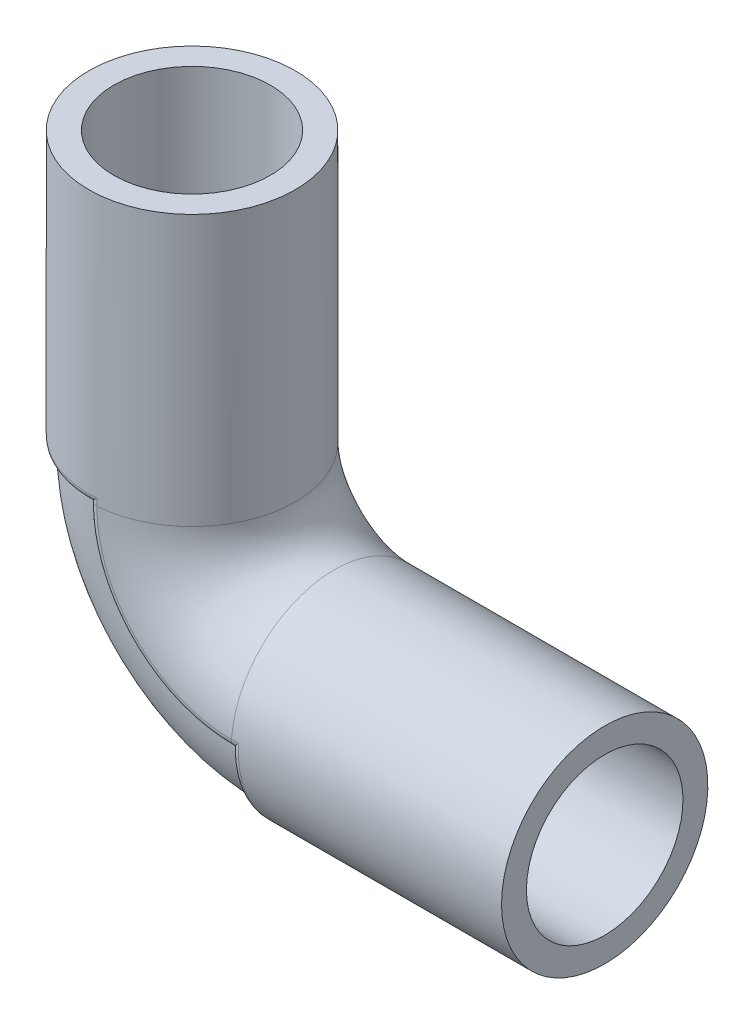
SolidWorks part; units mm, degrees
material "PVC 0.007 Plasticized"
ref_plane "Front Plane" through (0, 0, 0) normal (0, 0, 1) x (1, 0, 0)
ref_plane "Top Plane" through (0, 0, 0) normal (0, 1, 0) x (1, 0, 0)
ref_plane "Right Plane" through (0, 0, 0) normal (1, 0, 0) x (0, 0, -1)
sketch "Sketch1" plane through (0, 0, 0) normal (0, 0, 1) x (1, 0, 0)
  line L0 (0, 20) -> (0, 58)
  line L1 (20, 0) -> (58, 0)
  arc A0 (20, 0) -> (0, 20) centre (20, 20) cw
  point P3 (20, 0)
  point P5 (0, 20)
  point P8 (0, 0)
  dimension "D5" = 20
  dimension "D1" = 38
  dimension "D2" = 38
  dimension "D3" = 58
  dimension "D4" = 58
ref_plane "Plane1" through (0, 58, 0) normal (0, 1, 0) x (1, 0, 0)
sketch "Sketch2" plane through (0, 58, 0) normal (0, 1, 0) x (1, 0, 0)
  circle A0 centre (0, 0) radius 14.5
  circle A1 centre (0, 0) radius 11
sweep "Sweep1" add profiles "Sketch2" path "Sketch1"
sketch "Sketch3" plane through (0, 0, 0) normal (0, 0, 1) x (1, 0, 0)
  line L0 (14.5, 20) -> (-14.5, 20) construction
  line L1 (20, 14.5) -> (20, -14.5) construction
  arc A0 (0, 20) -> (20, 0) centre (20, 20) ccw
ref_plane "Plane2" through (0, 20, 0) normal (0, 1, 0) x (1, 0, 0)
sketch "Sketch4" plane through (0, 20, 0) normal (0, 1, 0) x (1, 0, 0)
  line L0 (0, -14.5) -> (0, -13.5)
  line L1 (0, 13.5) -> (0, 14.5)
  arc A0 (0, 14.5) -> (0, -14.5) centre (0, 0) ccw
  arc A2 (0, 13.5) -> (0, -13.5) centre (0, 0) ccw
  point P1 (12.5, 0)
  point P6 (0, 0)
  point P8 (13.8664, 4.2394)
sweep "Cut-Sweep1" cut profiles "Sketch4" path "Sketch3"
fillet "Fillet2" radius 1 2 edges at (-14.5, 20, 0) (20, -14.5, 0)
fillet "Fillet3" radius 1 6 edges at (5.8579, 5.8579, -14.5) (5.8579, 5.8579, 14.5)
